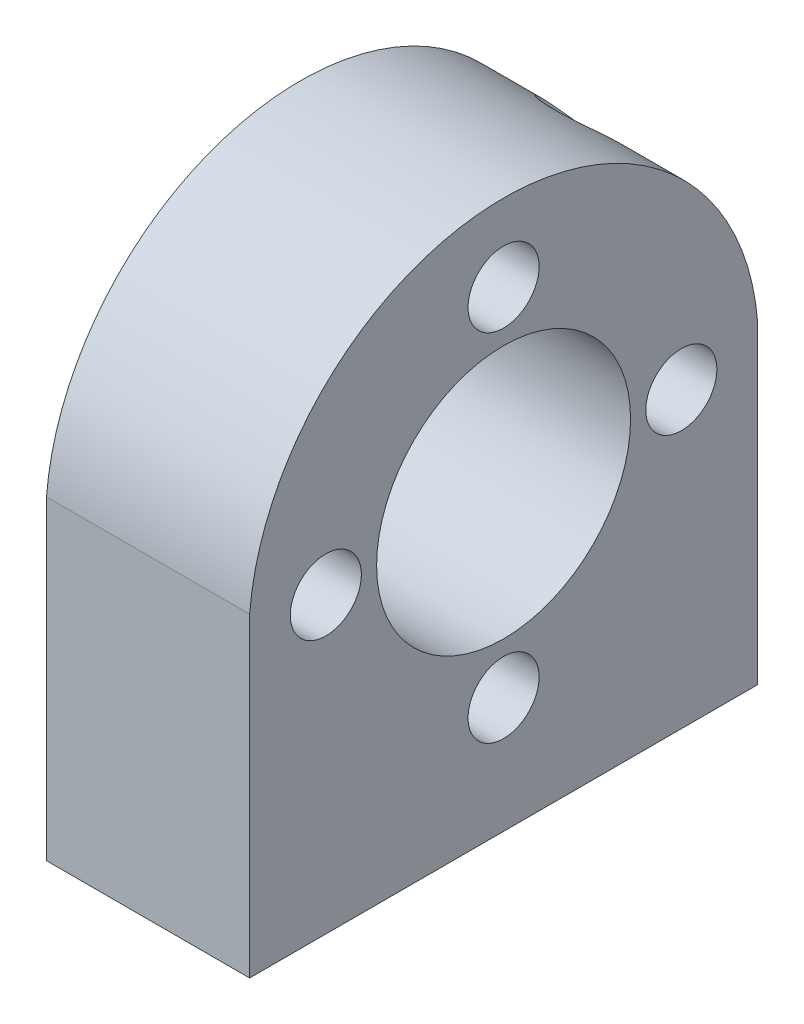
SolidWorks part; units mm, degrees
ref_plane "Ebene vorne" through (0, 0, 0) normal (0, 0, 1) x (1, 0, 0)
ref_plane "Ebene oben" through (0, 0, 0) normal (0, 1, 0) x (1, 0, 0)
ref_plane "Ebene rechts" through (0, 0, 0) normal (1, 0, 0) x (0, 0, -1)
sketch "Skizze1" plane through (0, 0, 0) normal (0, 1, 0) x (1, 0, 0)
  line L1 (-10, -25) -> (10, -25)
  line L2 (-10, -25) -> (-10, 25)
  line L3 (-10, 25) -> (10, 25)
  line L4 (10, -25) -> (10, 25)
  line L5 (-10, -25) -> (10, 25) construction
  line L6 (-10, 25) -> (10, -25) construction
  point P0 (0, 0)
  dimension "D1" = 20
  dimension "D2" = 50
extrude "Aufsatz-Linear austragen1" add sketch "Skizze1" along normal blind 54
sketch "Skizze2" plane through (-10, 0, 0) normal (-1, 0, 0) x (0, 0, 1)
  circle A0 centre (0, 28.9112) radius 25
  circle A1 centre (0, 28.9112) radius 12.5
  circle A2 centre (0, 28.9112) radius 17.5
  circle A3 centre (17.5, 28.9112) radius 2
  circle A4 centre (0, 11.4112) radius 2
  circle A5 centre (-17.5, 28.9112) radius 2
  circle A6 centre (0, 46.4112) radius 2
  point P15 (0, 28.9112)
  dimension "D1" = 25
  dimension "D2" = 35
  dimension "D3" = 4
extrude "Schnitt-Linear austragen1" cut sketch "Skizze2" against normal through all contours A2 A4 | A2 A5 | A2 A5 | A2 A4 | A2 A3 | A2 A3 | A1 | A6 region at (-10, 28.9112, 0) region at (-10, 28.9112, 16.6309) region at (-10, 28.9112, 18.3279) region at (-10, 10.5833, 0) region at (-10, 12.2803, 0) region at (-10, 28.9112, -16.6309) region at (-10, 28.9112, -18.3279)
sketch "Skizze3" plane through (0, 0, 0) normal (0, -1, 0) x (1, 0, 0)
  line L0 (0, 25) -> (0, -25) construction
  line L1 (-10, 25) -> (10, 25) construction
  line L2 (10, -25) -> (-10, -25) construction
  line L4 (0, 0) -> (3.2712, 0) construction
  circle A0 centre (0, 21) radius 2
  circle A1 centre (0, 11) radius 2
  circle A2 centre (0, -11) radius 2
  circle A3 centre (0, -21) radius 2
  dimension "D1" = 4
  dimension "D2" = 4
  dimension "D3" = 4
  dimension "D4" = 10
extrude "Schnitt-Linear austragen2" cut sketch "Skizze3" against normal blind 15 contours A0 | A1 | A2 | A3
sketch "Skizze4" plane through (10, 0, 0) normal (1, 0, 0) x (0, 0, -1)
  line L0 (-25.0888, 28.9112) -> (-25, 54)
  line L1 (-25, 54) -> (25, 54) construction
  line L2 (-25, 54) -> (-25, 0) construction
  line L3 (-25, 54) -> (25, 54)
  line L4 (25, 54) -> (25, 0) construction
  line L5 (25, 54) -> (25.0888, 28.9112)
  circle A0 centre (0, 28.9112) radius 25.0888
  line M8 (25, 0) -> (25, 54)
  line M9 (25, 54) -> (-25, 54)
  line M10 (-25, 54) -> (-25, 0)
extrude "Schnitt-Linear austragen3" cut sketch "Skizze4" against normal through all contours A0 L3 M10 | A0 M8 M9 region at (10, 48.4947, 19.3968) region at (10, 48.4947, -19.3968)
ref_plane "Ebene1" through (0, 32.1961, -32.1961) normal (0, 0.7071, -0.7071) x (1, 0, 0)
sketch "Skizze5" plane through (0, 32.1961, -32.1961) normal (0, 0.7071, -0.7071) x (1, 0, 0)
  circle A0 centre (0, -20) radius 4
  dimension "D2" = 8
  dimension "D1" = 20
extrude "Schnitt-Linear austragen4" cut sketch "Skizze5" against normal blind 18
sketch "Skizze6" plane through (10, 0, 0) normal (1, 0, 0) x (0, 0, -1)
  circle A0 centre (17.5, 28.9112) radius 3.5
  circle A1 centre (0, 11.4112) radius 3.5
  circle A2 centre (-17.5, 28.9112) radius 3.5
  circle A3 centre (0, 46.4112) radius 3.5
  point P11 (0, 28.9112)
  dimension "D1" = 7
  dimension "D2" = 4
extrude "Schnitt-Linear austragen5" cut sketch "Skizze6" against normal blind 10 contours A3 | A0 | A1 | A2
